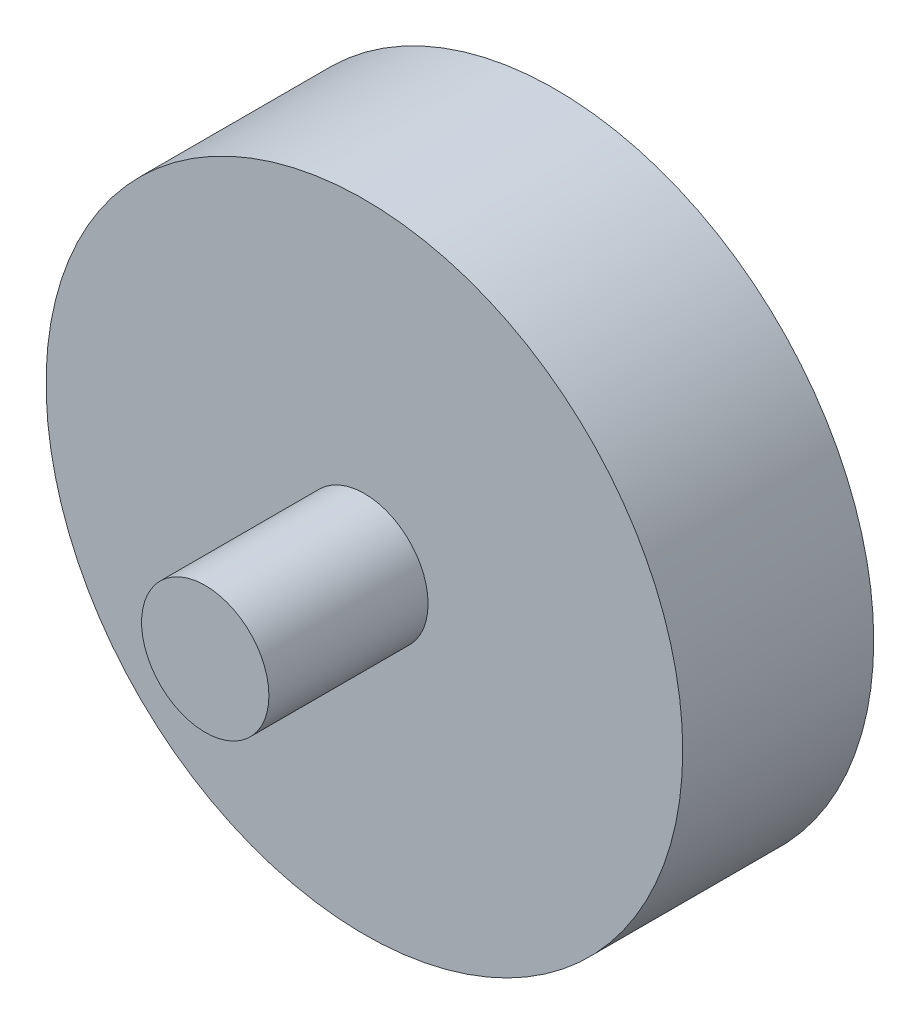
SolidWorks part; units mm, degrees
material "Natural Rubber"
ref_plane "Front Plane" through (0, 0, 0) normal (0, 0, 1) x (1, 0, 0)
ref_plane "Top Plane" through (0, 0, 0) normal (0, 1, 0) x (1, 0, 0)
ref_plane "Right Plane" through (0, 0, 0) normal (1, 0, 0) x (0, 0, -1)
sketch "Sketch1" plane through (0, 0, 0) normal (0, 0, 1) x (1, 0, 0)
  circle A0 centre (0, 0) radius 20
  dimension "D1" = 40
extrude "FOOT_BODY" add sketch "Sketch1" against normal blind 12
sketch "Sketch2" plane through (0, 0, 0) normal (0, 0, 1) x (1, 0, 0)
  circle A0 centre (0, 0) radius 4
  dimension "D1" = 8
extrude "M8_STUD" add sketch "Sketch2" along normal blind 10 separate body
sketch "Sketch3" plane through (0, 0, -12) normal (0, 0, -1) x (-1, 0, 0)
  circle A0 centre (0, 0) radius 15
  circle A1 centre (0, 0) radius 20 construction
  dimension "D1" = 30
extrude "Cut-Extrude1" cut sketch "Sketch3" against normal blind 1
chamfer "Chamfer1" distance 1 angle 45 1 edges at (-15, 0, -12)
